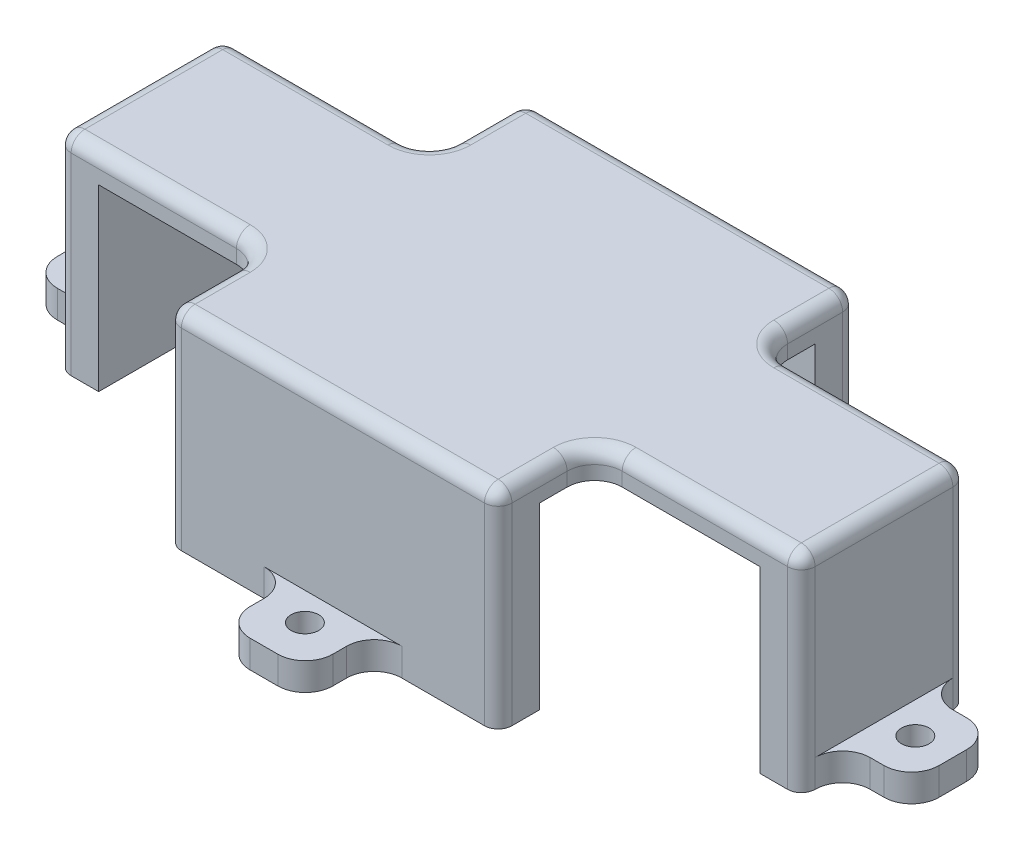
SolidWorks part; units mm, degrees
ref_plane "Front Plane" through (0, 0, 0) normal (0, 0, 1) x (1, 0, 0)
ref_plane "Top Plane" through (0, 0, 0) normal (0, 1, 0) x (1, 0, 0)
ref_plane "Right Plane" through (0, 0, 0) normal (1, 0, 0) x (0, 0, -1)
sketch "Sketch1" plane through (0, 0, 0) normal (0, 1, 0) x (1, 0, 0)
  line L0 (-3, -3) -> (51, -3)
  line L1 (0, 0) -> (48, 0)
  line L2 (0, 0) -> (0, 20)
  line L3 (0, 20) -> (48, 20)
  line L4 (48, 0) -> (48, 20)
  line L5 (51, -3) -> (51, 23)
  line L6 (-3, 23) -> (51, 23)
  line L7 (-3, -3) -> (-3, 23)
  dimension "D1" = 3
extrude "Boss-Extrude1" add sketch "Sketch1" along normal blind 13
sketch "Sketch2" plane through (0, 13, 0) normal (0, 1, 0) x (1, 0, 0)
  line L1 (-3, 23) -> (51, 23)
  line L2 (-3, 23) -> (-3, -3)
  line L3 (-3, -3) -> (51, -3)
  line L4 (51, 23) -> (51, -3)
extrude "Boss-Extrude2" add sketch "Sketch2" along normal blind 2
sketch "Sketch3" plane through (0, 15, 0) normal (0, 1, 0) x (1, 0, 0)
  line L0 (-3, 23) -> (12, 23)
  line L1 (51, 23) -> (-3, 23) construction
  line L2 (12, 23) -> (12, 16)
  line L3 (12, 16) -> (-3, 16)
  line L4 (-3, 23) -> (-3, -3) construction
  line L5 (-3, 16) -> (-3, 23)
  line L6 (-3, 10) -> (49997, 10) construction
  line L7 (24, 23) -> (24, -49977) construction
  line L8 (-3, 4) -> (-3, -3)
  line L9 (12, 4) -> (-3, 4)
  line L10 (12, -3) -> (12, 4)
  line L11 (-3, -3) -> (12, -3)
  line L12 (51, -3) -> (36, -3)
  line L13 (36, -3) -> (36, 4)
  line L14 (36, 4) -> (51, 4)
  line L15 (51, 4) -> (51, -3)
  line L16 (51, 16) -> (51, 23)
  line L17 (36, 16) -> (51, 16)
  line L18 (36, 23) -> (36, 16)
  line L19 (51, 23) -> (36, 23)
  point P11 (-3, 10)
  point P14 (24, 23)
extrude "Cut-Extrude1" cut sketch "Sketch3" against normal through all
fillet "Fillet1" radius 2 4 edges at (36, 14, -4) (12, 14, -4) (12, 14, -16) (36, 14, -16)
fillet "Fillet2" radius 1 24 edges at (3.5, 15, -16) (11.4142, 15, -16.5858) (3.5, 15, -4) (11.4142, 15, -3.4142) (36, 15, 0.5) (36.5858, 15, -3.4142) (44.5, 15, -16) (36.5858, 15, -16.5858) (-3, 7.5, -16) (12, 15, -20.5) (-3, 15, -10) (12, 7.5, 3) (36, 7.5, 3) (12, 15, 0.5) (24, 15, 3) (44.5, 15, -4) (51, 7.5, -4) (51, 7.5, -16) (51, 15, -10) (36, 15, -20.5) (12, 7.5, -23) (24, 15, -23) (36, 7.5, -23) (-3, 7.5, -4)
sketch "Sketch4" plane through (0, 0, 0) normal (0, -1, 0) x (1, 0, 0)
  line L0 (24, 3) -> (21, 3)
  line L1 (13, 3) -> (35, 3) construction
  line L2 (21, 3) -> (21, 6)
  line L3 (23, 8) -> (25, 8)
  line L4 (27, 6) -> (27, 3)
  line L5 (27, 3) -> (24, 3)
  line L6 (-3, -10) -> (49997, -10) construction
  line L7 (-3, -15) -> (-3, -5) construction
  line L8 (24, 8) -> (24, 3) construction
  line L9 (24, -28) -> (24, -23) construction
  line L10 (27, -23) -> (24, -23)
  line L11 (27, -26) -> (27, -23)
  line L12 (23, -28) -> (25, -28)
  line L13 (21, -23) -> (21, -26)
  line L14 (24, -23) -> (21, -23)
  line L15 (-3, -10) -> (-3, -7)
  line L16 (-3, -15) -> (-3, -5) construction
  line L17 (-3, -7) -> (-6, -7)
  line L18 (-8, -9) -> (-8, -11)
  line L19 (-6, -13) -> (-3, -13)
  line L20 (-3, -13) -> (-3, -10)
  line L21 (51, -13) -> (51, -10)
  line L22 (54, -13) -> (51, -13)
  line L23 (56, -9) -> (56, -11)
  line L24 (51, -7) -> (54, -7)
  line L25 (51, -10) -> (51, -7)
  arc A0 (23, 8) -> (21, 6) centre (23, 6) ccw
  arc A1 (27, 6) -> (25, 8) centre (25, 6) ccw
  circle A2 centre (24, 5.0341) radius 1
  circle A3 centre (24, -25.0341) radius 1
  arc A4 (27, -26) -> (25, -28) centre (25, -26) cw
  arc A5 (23, -28) -> (21, -26) centre (23, -26) cw
  arc A6 (-8, -9) -> (-6, -7) centre (-6, -9) cw
  arc A7 (-6, -13) -> (-8, -11) centre (-6, -11) cw
  circle A8 centre (-5.274, -10) radius 1
  circle A9 centre (53.274, -10) radius 1
  arc A10 (54, -13) -> (56, -11) centre (54, -11) ccw
  arc A11 (56, -9) -> (54, -7) centre (54, -9) ccw
  point P15 (-3, -10)
  dimension "D1" = 2
  dimension "D2" = 2
  dimension "D3" = 2
  dimension "D4" = 2
extrude "Boss-Extrude3" add sketch "Sketch4" against normal blind 2
fillet "Fillet3" radius 2 8 edges at (27, 1, 3) (21, 1, 3) (51, 1, -7) (51, 1, -13) (27, 1, -23) (21, 1, -23) (-3, 1, -13) (-3, 1, -7)
ref_plane "Plane1" through (24, 0, 0) normal (1, 0, 0) x (0, 0, -1)
ref_plane "Plane2" through (0, 0, -10) normal (0, 0, -1) x (-1, 0, 0)
